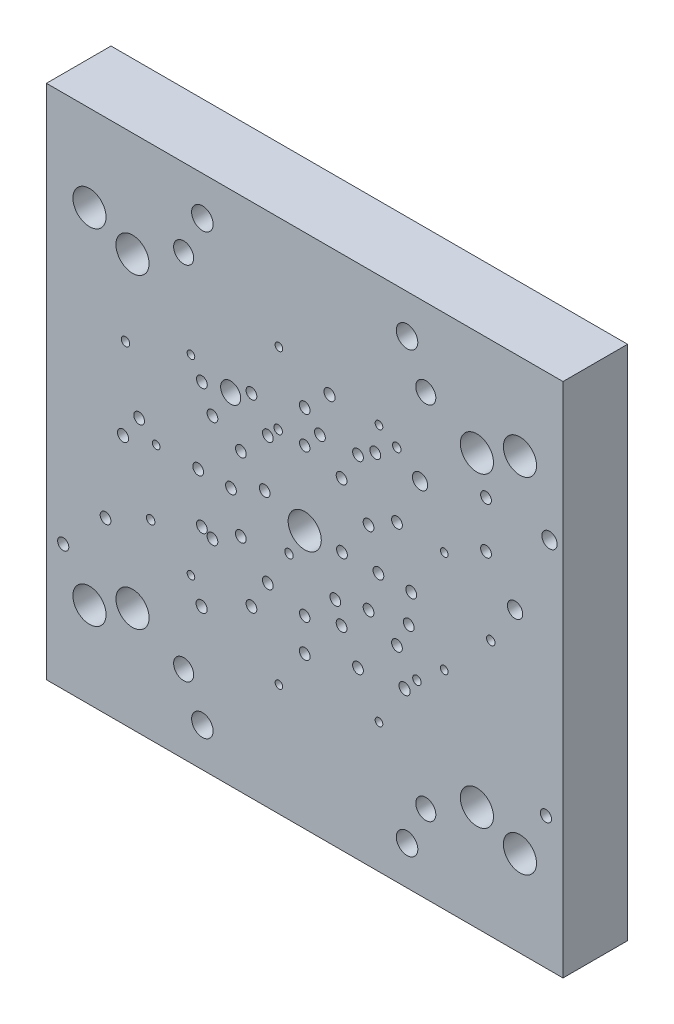
SolidWorks part; units mm, degrees
ref_plane "Front Plane" through (0, 0, 0) normal (0, 0, 1) x (1, 0, 0)
ref_plane "Top Plane" through (0, 0, 0) normal (0, 1, 0) x (1, 0, 0)
ref_plane "Right Plane" through (0, 0, 0) normal (1, 0, 0) x (0, 0, -1)
sketch "Sketch1" plane through (0, 0, 0) normal (0, 0, 1) x (1, 0, 0)
  line L1 (-152.4, 152.4) -> (152.4, 152.4)
  line L2 (-152.4, 152.4) -> (-152.4, -152.4)
  line L3 (-152.4, -152.4) -> (152.4, -152.4)
  line L4 (152.4, 152.4) -> (152.4, -152.4)
  line L5 (-152.4, 152.4) -> (152.4, -152.4) construction
  line L6 (-152.4, -152.4) -> (152.4, 152.4) construction
  point P0 (0, 0)
  dimension "D1" = 304.8
  dimension "D2" = 304.8
extrude "Boss-Extrude1" add sketch "Sketch1" along normal blind 38.1
sketch "Sketch2" plane through (0, 0, 38.1) normal (0, 0, 1) x (1, 0, 0)
  line L0 (-152.4, 0) -> (152.4, 0) construction
  line L5 (-152.4, 152.4) -> (-152.4, -152.4) construction
  line L6 (152.4, -152.4) -> (152.4, 152.4) construction
  line L7 (-152.4, -101.6) -> (152.4, -101.6) construction
  line L8 (-152.4, 101.6) -> (152.4, 101.6) construction
  line L9 (0, 101.6) -> (0, -101.6) construction
  line L10 (127, 101.6) -> (127, -101.6) construction
  line L11 (-127, 101.6) -> (-127, -101.6) construction
  circle A0 centre (-127, 101.6) radius 6.5151
  circle A1 centre (127, 101.6) radius 6.5151
  circle A2 centre (127, -101.6) radius 6.5151
  circle A3 centre (-127, -101.6) radius 6.5151
  circle A4 centre (0, 0) radius 6.5151
  dimension "D5" = 13.0302
  dimension "D1" = 101.6
  dimension "D2" = 101.6
  dimension "D3" = 127
  dimension "D4" = 127
extrude "HAAS T-Slot Holes" cut sketch "Sketch2" against normal through all
sketch "Sketch3" plane through (0, 0, 38.1) normal (0, 0, 1) x (1, 0, 0)
  circle A0 centre (-127, 101.6) radius 9.779
  circle A1 centre (127, 101.6) radius 9.779
  circle A2 centre (0, 0) radius 9.779
  circle A3 centre (127, -101.6) radius 9.779
  circle A4 centre (-127, -101.6) radius 9.779
  dimension "D1" = 19.558
extrude "HAAS Counter Bores" cut sketch "Sketch3" against normal offset from surface (22.225 mm away) 15.875 contours A0 | A1 | A2 | A3 | A4 up to face at (6.5151, 0, 0)
sketch "Sketch4" plane through (0, 0, 38.1) normal (0, 0, 1) x (1, 0, 0)
  line L0 (-127, 90.4875) -> (127, 90.4875) construction
  line L1 (-127, 30.1625) -> (127, 30.1625) construction
  line L2 (-127, 30.1625) -> (-127, -30.1625) construction
  line L3 (-127, -30.1625) -> (127, -30.1625) construction
  line L4 (127, 30.1625) -> (127, -30.1625) construction
  line L5 (-127, 30.1625) -> (127, -30.1625) construction
  line L6 (-127, -30.1625) -> (127, 30.1625) construction
  line L7 (-127, -90.4875) -> (127, -90.4875) construction
  line L8 (-101.6, 90.4875) -> (-101.6, 84.1375) construction
  line L9 (-101.6, -90.4875) -> (-101.6, -84.1375) construction
  line L10 (101.6, -90.4875) -> (101.6, -84.1375) construction
  line L11 (101.6, 90.4875) -> (101.6, 84.1375) construction
  circle A0 centre (-101.6, 90.4875) radius 6.5151
  circle A1 centre (101.6, 90.4875) radius 6.5151
  circle A2 centre (-101.6, -90.4875) radius 6.5151
  circle A3 centre (101.6, -90.4875) radius 6.5151
  point P0 (0, 0)
  dimension "D9" = 13.0302
  dimension "D1" = 60.325
  dimension "D2" = 254
  dimension "D5" = 203.2
  dimension "D6" = 25.4
  dimension "D7" = 203.2
  dimension "D8" = 6.35
  dimension "D3" = 60.325
  dimension "D4" = 60.325
extrude "Tormach T-Slot Holes" cut sketch "Sketch4" against normal through all
sketch "Sketch5" plane through (0, 0, 38.1) normal (0, 0, 1) x (1, 0, 0)
  circle A0 centre (-101.6, 90.4875) radius 9.779
  circle A1 centre (101.6, 90.4875) radius 9.779
  circle A2 centre (101.6, -90.4875) radius 9.779
  circle A3 centre (-101.6, -90.4875) radius 9.779
  dimension "D1" = 19.558
extrude "Tormach Counter bores" cut sketch "Sketch5" against normal up to surface (22.225 mm away) up to face at (-117.221, 101.6, 15.875)
sketch "Sketch6" plane through (0, 0, 38.1) normal (0, 0, 1) x (1, 0, 0)
  circle A0 centre (0, 0) radius 43.5 construction
  circle A1 centre (0, 43.5) radius 3.0734
  circle A2 centre (0, -43.5) radius 3.0734
  dimension "D1" = 87.0001
  dimension "D2" = 6.1468
extrude "Sprocket Locating Holes" cut sketch "Sketch6" against normal blind 6.35
sketch "Sketch7" plane through (0, 0, 38.1) normal (0, 0, 1) x (1, 0, 0)
  circle A0 centre (0, 0) radius 43.5 construction
  circle A2 centre (43.5, 0) radius 3.175
  circle A4 centre (37.6721, -21.75) radius 3.175
  circle A5 centre (21.75, -37.6721) radius 3.175
  circle A6 centre (0, -43.5) radius 3.175 [skipped]
  circle A7 centre (-21.75, -37.6721) radius 3.175
  circle A8 centre (-37.6721, -21.75) radius 3.175
  circle A9 centre (-43.5, 0) radius 3.175
  circle A10 centre (-37.6721, 21.75) radius 3.175
  circle A11 centre (-21.75, 37.6721) radius 3.175
  circle A12 centre (0, 43.5) radius 3.175 [skipped]
  circle A13 centre (21.75, 37.6721) radius 3.175
  circle A14 centre (37.6721, 21.75) radius 3.175
  point P31 (0, 0)
  dimension "D1" = 87.0001
  dimension "D2" = 6.35
  dimension "D3" = 12
extrude "Sprocket Mounting clearance holes" cut sketch "Sketch7" against normal blind 9.525
sketch "Sketch8" plane through (0, 0, 38.1) normal (0, 0, 1) x (1, 0, 0)
  line L1 (-71.4375, 106.4641) -> (71.4375, 106.4641) construction
  line L2 (-71.4375, 106.4641) -> (-71.4375, -106.4641) construction
  line L3 (-71.4375, -106.4641) -> (71.4375, -106.4641) construction
  line L4 (71.4375, 106.4641) -> (71.4375, -106.4641) construction
  line L5 (-71.4375, 106.4641) -> (71.4375, -106.4641) construction
  line L6 (-71.4375, -106.4641) -> (71.4375, 106.4641) construction
  circle A0 centre (-71.4375, 106.4641) radius 5.9182
  circle A1 centre (71.4375, 106.4641) radius 5.9182
  circle A2 centre (71.4375, -106.4641) radius 5.9182
  circle A3 centre (-71.4375, -106.4641) radius 5.9182
  point P0 (0, 0)
  dimension "D3" = 11.8364
  dimension "D1" = 142.875
  dimension "D2" = 212.9282
extrude "1/2-13 Tapped Holes" cut sketch "Sketch8" against normal blind 19.05
sketch "Sketch9" plane through (0, 0, 38.1) normal (0, 0, 1) x (1, 0, 0)
  circle A0 centre (-117.5189, -52.2876) radius 3.175
  circle A1 centre (-60.6634, -28.4101) radius 3.175
  circle A2 centre (-60.6634, 45.677) radius 3.175
  circle A3 centre (-23.6198, 8.6335) radius 3.175
  circle A4 centre (-97.707, 8.6335) radius 3.175
  circle A5 centre (18.0623, -26.1797) radius 3.175
  circle A6 centre (21.9762, 0) radius 3.175
  circle A7 centre (61.3833, -17.3739) radius 3.175
  circle A8 centre (106.976, 70.3959) radius 3.175
  circle A9 centre (106.976, 42.9004) radius 3.175
  circle A10 centre (144.4539, 67.4373) radius 4.5
  circle A11 centre (124.1092, 21.6131) radius 4.5
  circle A12 centre (68.0681, 59.3279) radius 4.5
  circle A13 centre (58.9353, -51.2652) radius 3.3
  circle A14 centre (-142.4923, -78.095) radius 3.3
  circle A15 centre (-105.7351, 43.7713) radius 2.5
  circle A16 centre (-90.8975, -39.8642) radius 2.5
  circle A17 centre (-9.2711, -16.3656) radius 2.5
  circle A18 centre (-15.6655, 43.8657) radius 2.5
  circle A20 centre (14.6267, 76.8405) radius 3.3
  circle A21 centre (8.9855, 53.4682) radius 3.175
  circle A22 centre (41.6559, 60.6579) radius 3.175
extrude "SSB Holes" cut sketch "Sketch9" against normal blind 19.05
ref_axis "Axis1" through (0, 0, 0) along (0, 0, 1)
sketch "Sketch10" plane through (0, 0, 38.1) normal (0, 0, 1) x (1, 0, 0)
  circle A0 centre (0, 0) radius 62.865 construction
  circle A1 centre (0, 62.865) radius 3.175
  circle A13 centre (31.4325, 54.4427) radius 3.175
  circle A14 centre (54.4427, 31.4325) radius 3.175
  circle A15 centre (62.865, 0) radius 3.175
  circle A16 centre (54.4427, -31.4325) radius 3.175
  circle A17 centre (31.4325, -54.4427) radius 3.175
  circle A18 centre (0, -62.865) radius 3.175
  circle A19 centre (-31.4325, -54.4427) radius 3.175
  circle A20 centre (-54.4427, -31.4325) radius 3.175
  circle A21 centre (-62.865, 0) radius 3.175
  circle A22 centre (-54.4427, 31.4325) radius 3.175
  circle A23 centre (-31.4325, 54.4427) radius 3.175
  point P30 (0, 0)
  point P56 (0, 0)
  dimension "D1" = 125.73
  dimension "D2" = 6.35
  dimension "D4" = 12
extrude "Sprocket Countersunk Holes" cut sketch "Sketch10" against normal blind 19.05
sketch "Sketch12" plane through (0, 0, 38.1) normal (0, 0, 1) x (1, 0, 0)
  circle A0 centre (-107.2144, -4.9977) radius 3.3
  circle A1 centre (-60.8212, -69.1392) radius 3.3
  circle A2 centre (142.3129, -74.567) radius 3.3
  circle A4 centre (54.3307, 69.7186) radius 2.4964
  circle A5 centre (109.7823, -1.2607) radius 2.5
  circle A6 centre (66.2094, -43.3332) radius 2.5
  circle A7 centre (-43.6886, 48.7489) radius 5.9182
  circle A8 centre (-71.4375, 106.4641) radius 5.9182 construction
extrude "DSB Holes" cut sketch "Sketch12" against normal blind 19.05
sketch "Brake Rotor Toe Clamp Holes" plane through (0, 0, 38.1) normal (0, 0, 1) x (1, 0, 0)
  line L0 (-55.0143, 117.9786) -> (55.0143, -117.9786) construction
  line L1 (55.0143, 117.9786) -> (-55.0143, -117.9786) construction
  line L2 (-55.0143, 117.9786) -> (-60.3816, 129.4887) construction
  line L3 (55.0143, 117.9786) -> (60.3816, 129.4887) construction
  line L4 (-55.0143, -117.9786) -> (-60.3816, -129.4887) construction
  line L5 (55.0143, -117.9786) -> (60.3816, -129.4887) construction
  line L6 (0, 0) -> (192.0367, 0) construction
  line L7 (0, 0) -> (-160.9096, 0) construction
  line L8 (0, 0) -> (0, 219.8313) construction
  line L9 (0, 0) -> (-215.8918, 38.0675) construction
  circle A0 centre (0, 0) radius 130.175 construction
  circle A6 centre (-60.3816, 129.4887) radius 6.35
  circle A7 centre (60.3816, 129.4887) radius 6.35
  circle A8 centre (60.3816, -129.4887) radius 6.35
  circle A9 centre (-60.3816, -129.4887) radius 6.35
  circle A10 centre (-87.63, 0) radius 2.3813 construction
  circle A12 centre (-74.93, 0) radius 2.3813 construction
  circle A13 centre (-80.0452, 14.1141) radius 2.3813
  circle A14 centre (-70.4112, 25.6276) radius 2.3812 construction
  circle A15 centre (-70.3905, 40.64) radius 2.3812 construction
  circle A16 centre (-82.3453, 29.9712) radius 2.3812 construction
  circle A17 centre (-57.3997, 48.1641) radius 2.3813 construction
  circle A18 centre (-52.2458, 62.2641) radius 2.3812
  circle A19 centre (-67.1285, 56.3275) radius 2.3812 construction
  circle A20 centre (-37.465, 64.8913) radius 2.3813 construction
  circle A21 centre (-27.7994, 76.3782) radius 2.3813 construction
  circle A22 centre (-43.815, 75.8898) radius 2.3813 construction
  circle A23 centre (-13.0115, 73.7916) radius 2.3813 construction
  circle A24 centre (0, 81.28) radius 2.3813
  circle A25 centre (-15.2168, 86.2987) radius 2.3813 construction
  circle A26 centre (13.0115, 73.7916) radius 2.3812 construction
  circle A27 centre (27.7994, 76.3782) radius 2.3812 construction
  circle A28 centre (15.2168, 86.2987) radius 2.3813 construction
  circle A29 centre (37.465, 64.8913) radius 2.3812 construction
  circle A30 centre (52.2458, 62.2641) radius 2.3813
  circle A31 centre (43.815, 75.8898) radius 2.3812 construction
  circle A32 centre (57.3997, 48.1641) radius 2.3813 construction
  circle A33 centre (70.3905, 40.64) radius 2.3813 construction
  circle A34 centre (67.1285, 56.3275) radius 2.3813 construction
  circle A35 centre (70.4112, 25.6276) radius 2.3813 construction
  circle A36 centre (80.0452, 14.1141) radius 2.3813
  circle A37 centre (82.3453, 29.9712) radius 2.3813 construction
  circle A38 centre (74.93, 0) radius 2.3813 construction
  circle A39 centre (80.0452, -14.1141) radius 2.3813 construction
  circle A40 centre (87.63, 0) radius 2.3813 construction
  circle A41 centre (70.4112, -25.6276) radius 2.3812 construction
  circle A42 centre (70.3905, -40.64) radius 2.3813
  circle A43 centre (82.3453, -29.9712) radius 2.3812 construction
  circle A44 centre (57.3997, -48.1641) radius 2.3813 construction
  circle A45 centre (52.2458, -62.2641) radius 2.3813 construction
  circle A46 centre (67.1285, -56.3275) radius 2.3812 construction
  circle A47 centre (37.465, -64.8913) radius 2.3813 construction
  circle A48 centre (27.7994, -76.3782) radius 2.3813
  circle A49 centre (43.815, -75.8898) radius 2.3813 construction
  circle A50 centre (13.0115, -73.7916) radius 2.3813 construction
  circle A51 centre (0, -81.28) radius 2.3812 construction
  circle A52 centre (15.2168, -86.2987) radius 2.3813 construction
  circle A53 centre (-13.0115, -73.7916) radius 2.3813 construction
  circle A54 centre (-27.7994, -76.3782) radius 2.3813
  circle A55 centre (-15.2168, -86.2987) radius 2.3813 construction
  circle A56 centre (-37.465, -64.8913) radius 2.3813 construction
  circle A57 centre (-52.2458, -62.2641) radius 2.3813 construction
  circle A58 centre (-43.815, -75.8898) radius 2.3812 construction
  circle A59 centre (-57.3997, -48.1641) radius 2.3813 construction
  circle A60 centre (-70.3905, -40.64) radius 2.3813
  circle A61 centre (-67.1285, -56.3275) radius 2.3813 construction
  circle A62 centre (-70.4112, -25.6276) radius 2.3813 construction
  circle A63 centre (-80.0452, -14.1141) radius 2.3813 construction
  circle A64 centre (-82.3453, -29.9712) radius 2.3813 construction
  point P26 (0, 0)
  point P27 (0, 0)
  point P28 (0, 0)
  point P130 (0, 0)
  point P131 (0, 0)
  dimension "D1" = 260.35
  dimension "D2" = 12.7
  dimension "D3" = 12.7
  dimension "D4" = 12.7
  dimension "D5" = 12.7
  dimension "D17" = 4.7625
  dimension "D18" = 81.28
  dimension "D19" = 18
  dimension "D14" = 4.7625
  dimension "D15" = 4.7625
  dimension "D6" = 12.7
  dimension "D7" = 12.7
  dimension "D8" = 12.7
  dimension "D9" = 12.7
  dimension "D10" = 65
  dimension "D11" = 65
  dimension "D12" = 87.63
  dimension "D13" = 12.7
  dimension "D16" = 10
hole_wizard "Rotor Clamp Bolts" positions "Sketch15" profile "Sketch16" hole size "M4" standard "AS"
sketch "Sketch15" plane through (0, 0, 38.1) normal (0, 0, 1) x (1, 0, 0)
  point P0 (-87.63, 0)
  point P3 (-67.1285, -56.3275)
  point P6 (-15.2168, -86.2987)
  point P9 (43.815, -75.8898)
  point P12 (82.3453, -29.9712)
  point P15 (82.3453, 29.9712)
  point P18 (43.815, 75.8898)
  point P21 (-15.2168, 86.2987)
  point P24 (-67.1285, 56.3275)
sketch "Sketch16" plane through (-87.63, 0, 38.1) normal (1, 0, 0) x (0, -1, 0)
  line L0 (0, 0) -> (0, 20.4019)
  line L1 (0, 20.4019) -> (2.25, 19.05)
  line L2 (2.25, 19.05) -> (2.25, 0)
  line L5 (2.25, 0) -> (0, 0)
  line L10 (0, 20.4019) -> (-2.25, 19.05) construction
  line L11 (0, -6.35) -> (0, 107.95) construction
  dimension "Hole Dia." = 4.5
  dimension "Hole Depth" = 19.05
  dimension "Drill Angle" = 118
extrude "Outer Toe Clamp" cut sketch "Brake Rotor Toe Clamp Holes" against normal blind 19.05 contours A8 | A9 | A7 | A6
equation "\"boltRotor\"=0.75"
equation "\"bolt\"=0.51159"
